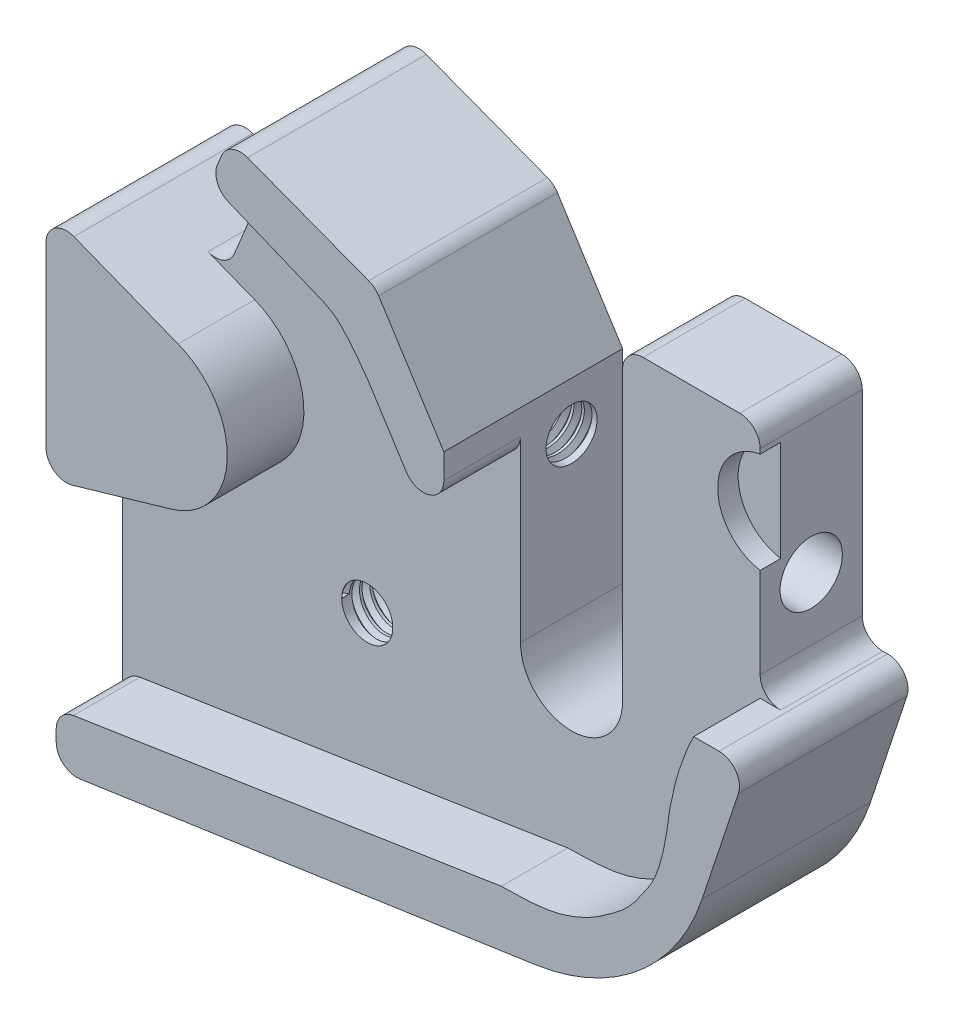
SolidWorks part; units mm, degrees
ref_plane "Front Plane" through (0, 0, 0) normal (0, 0, 1) x (1, 0, 0)
ref_plane "Top Plane" through (0, 0, 0) normal (0, 1, 0) x (1, 0, 0)
ref_plane "Right Plane" through (0, 0, 0) normal (1, 0, 0) x (0, 0, -1)
sketch "Sketch1" plane through (0, 0, 0) normal (0, 0, 1) x (1, 0, 0)
  line L0 (169.0465, 531.5792) -> (1384.9618, 942.3347) construction
  line L1 (17.1755, 0.269) -> (145.8355, -18.3486) construction
  line L2 (78.9683, 43.5936) -> (88.9683, 43.5936)
  line L3 (88.9683, 43.5936) -> (88.9683, 26.5936)
  line L4 (88.9683, 26.5936) -> (78.9683, 26.5936)
  line L5 (78.9683, 26.5936) -> (78.9683, 43.5936)
  line L6 (77.9414, 43.8024) -> (71.5407, 53.8656)
  line L7 (56.0381, 62.9033) -> (67.1668, 58.333)
  line L8 (88.9683, 43.5936) -> (88.9683, 61.7655)
  line L9 (88.9683, 61.7655) -> (102.4319, 61.7655)
  line L10 (77.9414, 43.8024) -> (78.9683, 42.1878)
  line L11 (20.6229, 24.1202) -> (53.1029, 33.5417)
  line L12 (23.9133, 59.0209) -> (55.1963, 46.7648)
  line L13 (56.0381, 62.9033) -> (50.2123, 48.7174)
  line L14 (70.5008, 62.7543) -> (72.231, 62.0968)
  line L15 (20.6228, 1.7639) -> (20.6229, 24.1202)
  line L16 (20.6229, 24.1202) -> (20.6229, 30.1202)
  line L17 (103.2745, 61.7655) -> (102.4319, 61.7655)
  line L18 (20.6229, 30.1202) -> (43.6301, 36.7939)
  line L19 (23.9133, 59.0209) -> (22.0894, 54.3655)
  line L20 (22.0894, 54.3655) -> (44.4958, 45.587)
  line L21 (78.9683, 43.5936) -> (78.9683, 49.4415)
  line L22 (57.9376, 67.5285) -> (70.5008, 62.7543)
  line L23 (83.9683, 38.5936) -> (107.6777, 38.5936)
  line L24 (40.0198, 35.7467) -> (40.0198, 47.3406)
  line L25 (40.0198, 47.3406) -> (40.0198, 52.7107)
  line L26 (56.0381, 62.9033) -> (57.9376, 67.5285)
  line L27 (103.4635, 40.5809) -> (108.336, 40.5809) construction
  line L28 (40.0198, 35.7467) -> (40.0198, 4.6135)
  line L29 (108.336, 40.5809) -> (99.307, 13.3233)
  line L30 (102.4319, 61.7655) -> (102.4319, 40.5809)
  line L31 (99.307, 13.3233) -> (20.6228, 1.7639)
  line L32 (83.9683, 43.5936) -> (83.9683, 46.6936)
  line L33 (20.6228, 6.4639) -> (20.6228, 6.7639)
  line L34 (20.6228, 6.7639) -> (83.6, 16.4882)
  line L35 (20.6229, 30.1202) -> (20.6229, 61.7655)
  line L36 (23.9133, 59.0209) -> (20.6229, 60.3101)
  line L37 (22.0894, 54.3655) -> (20.6229, 54.94)
  line L38 (73.7743, 50.3539) -> (77.9932, 53.0374) construction
  line L39 (77.9932, 53.0374) -> (71.1704, 63.7644)
  line L40 (77.9932, 53.0374) -> (78.9683, 51.5043)
  line L41 (78.9683, 51.5043) -> (78.9683, 49.4415)
  line L42 (102.4319, 40.5809) -> (102.4319, 38.5936)
  line L47 (102.4319, 40.5809) -> (103.4635, 40.5809) construction
  circle A0 centre (83.9683, 31.5936) radius 5
  circle A1 centre (83.9683, 38.5936) radius 5
  circle A5 centre (50.1903, 40.5872) radius 7.578
  circle A6 centre (103.2745, 54.3655) radius 4.4
  circle A7 centre (103.2745, 54.3655) radius 7.4
  circle A8 centre (83.9683, 31.5936) radius 20.3057
  spline S0 degree 3 poles (67.1668, 58.333) (67.5307, 58.1482) (68.2163, 57.8297) (69.7375, 56.3376) (70.7671, 54.998) (71.5407, 53.8656) knots 0 0 0 0 0.194176 0.353383 1 1 1 1
  spline S1 degree 3 poles (83.6, 16.4882) (85.4172, 16.5376) (87.878, 16.5192) (90.6726, 17.4205) (92.3949, 18.1773) (94.0998, 19.3373) (95.7619, 20.5842) (96.8381, 21.8934) (97.5722, 23.0215) (98.2993, 24.0127) (98.8168, 25.1807) (99.3382, 26.7948) (99.7545, 28.7331) (99.9792, 30.8782) (100.4112, 32.873) (100.8434, 34.6928) (101.4168, 36.2088) (101.8572, 37.4461) (102.3579, 38.4137) (102.8415, 39.4999) (103.165, 40.2018) (103.4635, 40.5809) knots 0 0 0 0 0.157684 0.206761 0.251698 0.319001 0.383658 0.429514 0.463788 0.499543 0.534878 0.573031 0.645405 0.704849 0.75836 0.820852 0.865423 0.897677 0.933689 0.958942 1 1 1 1
  spline S2 degree 3 poles (103.4635, 40.5809) (103.5281, 40.7021) (103.6539, 40.9177) (103.7777, 41.1891) (104.0324, 41.5752) (104.2845, 42.0418) (104.6133, 42.6639) (105.0506, 43.3284) (105.5376, 44.1633) (106.1189, 44.9679) (106.7473, 45.8247) (107.3304, 46.576) (107.8594, 47.2965) (108.3783, 47.8664) (108.8492, 48.4246) (109.2415, 48.9281) (109.5877, 49.4941) (110.1609, 50.7988) (110.3782, 52.0409) (110.5419, 52.9707) knots 0 0 0 0 0.032133 0.040138 0.080049 0.114202 0.15475 0.224504 0.279876 0.355143 0.430433 0.500504 0.552615 0.615873 0.660356 0.704255 0.748281 0.797656 1 1 1 1
  point P13 (0, 0)
  dimension "D7" = 5
  dimension "D5" = 8.8
  dimension "D6" = 14.8
  dimension "D1" = 130
  dimension "D2" = 10
  dimension "D3" = 17
  dimension "D8" = 5
  dimension "D9" = 5
  dimension "D10" = 5
extrude "Boss-Extrude1" add sketch "Sketch1" along normal blind 10 contours L34 S1 A8 L47 L30 L8 L3 L4 L5 L10 L6 | S0 L7 L13 L12 A5 L11 L28 L34 A8 L6 | A0 L5 L4 | A0 L4 L3 | A8 L30 A7 L9 L8 | L30 A7 | L30 A8 L8 L3 L23 L42 | L30 A6 region at (78.4481, 40.3907, 0) region at (94.3714, 43.544, 0) region at (94.5751, 54.1796, 0) region at (87.8514, 27.7104, 0) region at (80.0851, 27.7104, 0) region at (56.6282, 32.8832, 0) region at (102.2709, 60.2007, 0) region at (100.9442, 54.3655, 0)
extrude "Boss-Extrude2" add sketch "Sketch1<3>" along normal blind 17.5 contours L7 S0 L6 A8 L41 L40 L39 L14 L22 L26 | L41 A8 L6 L10 L5 L21 | A5 | A5 L12 L25 L20 | A5 L20 L24 L18 | A5 L18 L28 L11 region at (77.4058, 47.7092, 0) region at (68.0812, 59.4299, 0) region at (43.4702, 33.1986, 0) region at (43.8977, 48.9301, 0) region at (50.1903, 40.5872, 0) region at (41.5617, 41.668, 0)
sketch "Sketch1<3>" plane through (0, 0, 0) normal (0, 0, 1) x (1, 0, 0) same geometry as "Sketch1"
extrude "Boss-Extrude3" add sketch "Sketch1<4>" along normal blind 16.5 contours A8 L29 L23 | S1 L34 A8 L23 | A8 L34 L28 L31 region at (102.7306, 38.1752, 0) region at (105.1657, 35.2144, 0) region at (58.9314, 9.8932, 0)
sketch "Sketch1<4>" plane through (0, 0, 0) normal (0, 0, 1) x (1, 0, 0) same geometry as "Sketch1"
sketch "Sketch4" plane through (88.9683, 0, 0) normal (-1, 0, 0) x (0, 0, 1)
  line L0 (5, 61.7655) -> (5, 46.7655)
  line L2 (10, 61.7655) -> (0, 61.7655) construction
  circle A0 centre (5, 46.7655) radius 3.05
  dimension "D1" = 15
extrude "Cut-Extrude2" cut sketch "Sketch4" against normal blind 30 contours A0 region at (88.9683, 44.6698, 2.9043)
hole_wizard "Tap Drill for M6x1.0 Tap3" positions "3DSketch7" profile "Sketch10" hole size "M6x1.0" standard "ANSI Metric"
sketch3d "3DSketch7"
  line L0 (102.4319, 46.7655, 5) -> (88.9683, 46.7655, 5) construction
  point P0 (88.9683, 46.7655, 5)
sketch "Sketch10" plane through (88.9683, 46.7655, 5) normal (0, 1, 0) x (0, 0, -1)
  line L0 (0, 0) -> (0, 31.5022)
  line L1 (0, 31.5022) -> (2.5, 30)
  line L2 (2.5, 30) -> (2.5, 0)
  line L5 (2.5, 0) -> (0, 0)
  line L10 (0, 31.5022) -> (-2.5, 30) construction
  line L11 (0, -6.35) -> (0, 107.95) construction
  dimension "Hole Dia." = 5
  dimension "Hole Depth" = 30
  dimension "Drill Angle" = 118
thread "Thread2" pitch 1 method cut profile "Thread Profile2" start angle 0, offset 0, length 20, pitch 1, diameter 5
ref_plane "Plane2" through (78.9683, 46.7655, 7.5) normal (0, -1, 0) x (0, 0, 1)
sketch "Thread Profile2" plane through (78.9683, 46.7655, 7.5) normal (0, -1, 0) x (0, 0, 1)
  line L0 (0, 0) -> (0, 1) construction
  line L1 (0, 0) -> (0.5413, 0.3125)
  line L2 (0.5413, 0.3125) -> (0.5413, 0.4375)
  line L3 (0.5413, 0.4375) -> (0, 0.75)
  line L4 (0.5413, 0.375) -> (0, 0.375) construction
  line L11 (0, 0) -> (0, 0.75)
  point P2 (0, 0)
  dimension "Pitch" = 1
  dimension "Profile_Angle" = 60
  dimension "Profile_Land" = 0.125
  dimension "Profile_Height" = 0.5413
sketch "Sketch14" plane through (0, 0, 10) normal (0, 0, 1) x (1, 0, 0)
  line L0 (83.9683, 26.5936) -> (63.9683, 26.5936)
  arc A0 (78.9683, 31.5936) -> (88.9683, 31.5936) centre (83.9683, 31.5936) ccw construction
hole_wizard "Tap Drill for M6x1.0 Tap4" positions "3DSketch11" profile "Sketch15" hole size "M6x1.0" standard "ANSI Metric"
sketch3d "3DSketch11"
  point P0 (63.9683, 26.5936, 10)
sketch "Sketch15" plane through (63.9683, 26.5936, 10) normal (1, 0, 0) x (0, -1, 0)
  line L0 (0, 0) -> (0, 31.5022)
  line L1 (0, 31.5022) -> (2.5, 30)
  line L2 (2.5, 30) -> (2.5, 0)
  line L5 (2.5, 0) -> (0, 0)
  line L10 (0, 31.5022) -> (-2.5, 30) construction
  line L11 (0, -6.35) -> (0, 107.95) construction
  dimension "Hole Dia." = 5
  dimension "Hole Depth" = 30
  dimension "Drill Angle" = 118
thread "Thread3" pitch 1 method cut profile "Thread Profile3" start angle 0, offset 0, length 20, pitch 1, diameter 5
ref_plane "Plane3" through (61.4683, 26.5936, 10) normal (0, -1, 0) x (-1, 0, 0)
sketch "Thread Profile3" plane through (61.4683, 26.5936, 10) normal (0, -1, 0) x (-1, 0, 0)
  line L0 (0, 0) -> (0, 1) construction
  line L1 (0, 0) -> (0.5413, 0.3125)
  line L2 (0.5413, 0.3125) -> (0.5413, 0.4375)
  line L3 (0.5413, 0.4375) -> (0, 0.75)
  line L4 (0.5413, 0.375) -> (0, 0.375) construction
  line L11 (0, 0) -> (0, 0.75)
  point P2 (0, 0)
  dimension "Pitch" = 1
  dimension "Profile_Angle" = 60
  dimension "Profile_Land" = 0.125
  dimension "Profile_Height" = 0.5413
fillet "Fillet1" radius 2 13 edges at (102.4319, 61.7655, 5) (88.9683, 61.7655, 5) (57.9376, 67.5285, 8.75) (56.0381, 62.9033, 13.75) (78.9683, 42.1878, 13.75) (50.2123, 48.7174, 5) (40.0198, 29.7467, 13.75) (40.0198, 52.7107, 8.75) (72.231, 62.0968, 8.75) (40.0198, 4.6135, 8.25) (40.0198, 9.759, 13.25) (107.6777, 38.5936, 8.25) (102.4319, 38.5936, 5)
sketch "Sketch16" plane through (0, 0, 10) normal (0, 0, 1) x (1, 0, 0)
  line L0 (78.9683, 43.5936) -> (88.9683, 43.5936)
  line L1 (88.9683, 43.5936) -> (88.9683, 26.5936)
  line L2 (88.9683, 26.5936) -> (78.9683, 26.5936)
  line L3 (78.9683, 26.5936) -> (78.9683, 43.5936)
  line L4 (77.9414, 43.8024) -> (71.5407, 53.8656)
  line L5 (56.0381, 62.9033) -> (67.1668, 58.333)
  line L6 (88.9683, 43.5936) -> (88.9683, 61.7655)
  line L7 (88.9683, 61.7655) -> (102.4319, 61.7655)
  line L8 (77.9414, 43.8024) -> (78.9683, 42.1878)
  line L9 (20.6229, 24.1202) -> (53.1029, 33.5417)
  line L10 (23.9133, 59.0209) -> (55.1963, 46.7648)
  line L11 (56.0381, 62.9033) -> (50.2123, 48.7174)
  line L12 (70.5008, 62.7543) -> (72.231, 62.0968)
  line L13 (20.6228, 1.7639) -> (20.6229, 24.1202)
  line L14 (20.6229, 24.1202) -> (20.6229, 30.1202)
  line L15 (103.2745, 61.7655) -> (102.4319, 61.7655)
  line L16 (20.6229, 30.1202) -> (43.6301, 36.7939)
  line L17 (23.9133, 59.0209) -> (22.0894, 54.3655)
  line L18 (22.0894, 54.3655) -> (44.4958, 45.587)
  line L19 (78.9683, 43.5936) -> (78.9683, 49.4415)
  line L20 (57.9376, 67.5285) -> (70.5008, 62.7543)
  line L21 (83.9683, 38.5936) -> (107.6777, 38.5936)
  line L22 (40.0198, 35.7467) -> (40.0198, 47.3406)
  line L23 (40.0198, 47.3406) -> (40.0198, 52.7107)
  line L24 (56.0381, 62.9033) -> (57.9376, 67.5285)
  line L25 (103.4635, 40.5809) -> (108.336, 40.5809) construction
  line L26 (40.0198, 35.7467) -> (40.0198, 4.6135)
  line L27 (108.336, 40.5809) -> (99.307, 13.3233)
  line L28 (102.4319, 61.7655) -> (102.4319, 40.5809)
  line L29 (99.307, 13.3233) -> (20.6228, 1.7639)
  line L30 (83.9683, 43.5936) -> (83.9683, 46.6936)
  line L31 (20.6228, 6.4639) -> (20.6228, 6.7639)
  line L32 (20.6228, 6.7639) -> (83.6, 16.4882)
  line L33 (20.6229, 30.1202) -> (20.6229, 61.7655)
  line L34 (23.9133, 59.0209) -> (20.6229, 60.3101)
  line L35 (22.0894, 54.3655) -> (20.6229, 54.94)
  line L36 (73.7743, 50.3539) -> (77.9932, 53.0374) construction
  line L37 (77.9932, 53.0374) -> (71.1704, 63.7644)
  line L38 (77.9932, 53.0374) -> (78.9683, 51.5043)
  line L39 (78.9683, 51.5043) -> (78.9683, 49.4415)
  line L40 (102.4319, 40.5809) -> (102.4319, 38.5936)
  line L41 (102.4319, 40.5809) -> (103.4635, 40.5809) construction
  circle A0 centre (83.9683, 31.5936) radius 5
  circle A1 centre (83.9683, 38.5936) radius 5
  circle A2 centre (50.1903, 40.5872) radius 7.578
  circle A3 centre (103.2745, 54.3655) radius 4.4
  circle A4 centre (103.2745, 54.3655) radius 7.4
  circle A5 centre (83.9683, 31.5936) radius 20.3057
  circle A6 centre (103.2745, 54.3655) radius 5
  spline S0 degree 3 poles (67.1668, 58.333) (67.5307, 58.1482) (68.2163, 57.8297) (69.7375, 56.3376) (70.7671, 54.998) (71.5407, 53.8656) knots 0 0 0 0 0.194176 0.353383 1 1 1 1
  spline S1 degree 3 poles (83.6, 16.4882) (85.4172, 16.5376) (87.878, 16.5192) (90.6726, 17.4205) (92.3949, 18.1773) (94.0998, 19.3373) (95.7619, 20.5842) (96.8381, 21.8934) (97.5722, 23.0215) (98.2993, 24.0127) (98.8168, 25.1807) (99.3382, 26.7948) (99.7545, 28.7331) (99.9792, 30.8782) (100.4112, 32.873) (100.8434, 34.6928) (101.4168, 36.2088) (101.8572, 37.4461) (102.3579, 38.4137) (102.8415, 39.4999) (103.165, 40.2018) (103.4635, 40.5809) knots 0 0 0 0 0.157684 0.206761 0.251698 0.319001 0.383658 0.429514 0.463788 0.499543 0.534878 0.573031 0.645405 0.704849 0.75836 0.820852 0.865423 0.897677 0.933689 0.958942 1 1 1 1
  spline S2 degree 3 poles (103.4635, 40.5809) (103.5281, 40.7021) (103.6539, 40.9177) (103.7777, 41.1891) (104.0324, 41.5752) (104.2845, 42.0418) (104.6133, 42.6639) (105.0506, 43.3284) (105.5376, 44.1633) (106.1189, 44.9679) (106.7473, 45.8247) (107.3304, 46.576) (107.8594, 47.2965) (108.3783, 47.8664) (108.8492, 48.4246) (109.2415, 48.9281) (109.5877, 49.4941) (110.1609, 50.7988) (110.3782, 52.0409) (110.5419, 52.9707) knots 0 0 0 0 0.032133 0.040138 0.080049 0.114202 0.15475 0.224504 0.279876 0.355143 0.430433 0.500504 0.552615 0.615873 0.660356 0.704255 0.748281 0.797656 1 1 1 1
  dimension "D3" = 8.8
  dimension "D4" = 14.8
  dimension "D1" = 10
  dimension "D2" = 17
  dimension "D5" = 5
  dimension "D6" = 5
  dimension "D7" = 5
  dimension "D8" = 5
extrude "Cut-Extrude3" cut sketch "Sketch16" against normal blind 2 contours A6
